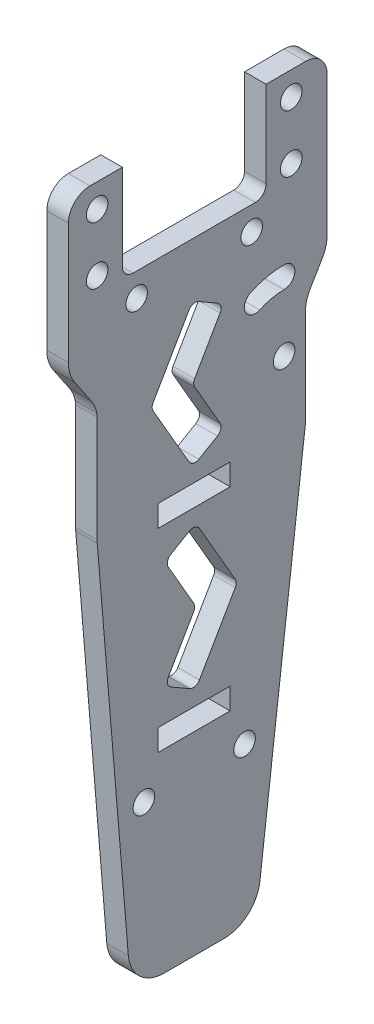
SolidWorks part; units mm, degrees
ref_plane "Płaszczyzna przednia" through (0, 0, 0) normal (0, 0, 1) x (1, 0, 0)
ref_plane "Płaszczyzna górna" through (0, 0, 0) normal (0, 1, 0) x (1, 0, 0)
ref_plane "Płaszczyzna prawa" through (0, 0, 0) normal (1, 0, 0) x (0, 0, -1)
ref_plane "Płaszczyzna1" through (-2, 0, 0) normal (-1, 0, 0) x (0, -1, 0)
sketch "Szkic1" plane through (-2, 0, 0) normal (-1, 0, 0) x (0, -1, 0)
  line L2 (-20.2446, -15.5) -> (-6.8721, -15.5)
  line L3 (-6.2672, -15.4633) -> (45.605, -9.1406)
  line L4 (50, -4.1773) -> (50, 4.1773)
  line L5 (45.4155, 9.16) -> (-6.4254, 13.4827)
  line L6 (-6.8408, 13.5) -> (-21.6327, 13.5)
  line L7 (-24.0036, 14.3214) -> (-27.4134, 16.6366)
  line L8 (-30.2221, 17.5) -> (-47, 17.5)
  line L9 (-50, 14.5) -> (-50, 10)
  line L10 (-50, 10) -> (-38, 10)
  line L11 (-36.5, 8.5) -> (-36.5, -8.5)
  line L12 (-38, -10) -> (-50, -10)
  line L13 (-50, -10) -> (-50, -15.5)
  line L14 (-47, -18.5) -> (-27.6426, -18.5)
  line L15 (-25.1042, -17.8077) -> (-22.283, -16.1452)
  line L16 (-46.7, 13.5) -> (-46.7, -13.5) construction
  line L17 (-33.2, 8) -> (-33.2, -8) construction
  line L18 (-38.7, 13.5) -> (-38.7, -13.5) construction
  line L19 (0, 0) -> (50, 0) construction
  line L20 (0, 0) -> (-45, 0) construction
  circle A0 centre (-46.7, -13.5) radius 1.5
  circle A1 centre (-38.7, -13.5) radius 1.5
  circle A2 centre (-33.2, -8) radius 1.5
  circle A3 centre (-33.2, 8) radius 1.5
  circle A4 centre (-38.7, 13.5) radius 1.5
  circle A5 centre (-46.7, 13.5) radius 1.5
  arc A6 (-6.4254, 13.4827) -> (-6.8408, 13.5) centre (-6.8408, 8.5) ccw
  arc A7 (-6.8721, -15.5) -> (-6.2672, -15.4633) centre (-6.8721, -10.5) ccw
  arc A12 (-22.283, -16.1452) -> (-20.6825, -15.5417) centre (-19.7445, -20.4529) cw
  arc A13 (45.605, -9.1406) -> (50, -4.1773) centre (45, -4.1773) ccw
  arc A14 (50, 4.1773) -> (45.4155, 9.16) centre (45, 4.1773) ccw
  arc A15 (-22.1331, 13.5467) -> (-24.0036, 14.3214) centre (-21.1949, 18.4579) cw
  arc A16 (-27.4134, 16.6366) -> (-30.2221, 17.5) centre (-30.2221, 12.5) ccw
  arc A17 (-47, 17.5) -> (-50, 14.5) centre (-47, 14.5) ccw
  arc A18 (-38, 10) -> (-36.5, 8.5) centre (-38, 8.5) cw
  arc A19 (-36.5, -8.5) -> (-38, -10) centre (-38, -8.5) cw
  arc A20 (-50, -15.5) -> (-47, -18.5) centre (-47, -15.5) ccw
  arc A21 (-27.6426, -18.5) -> (-25.1042, -17.8077) centre (-27.6426, -13.5) ccw
  spline S0 degree 3 poles (-20.2446, -15.5) (-20.3911, -15.5) (-20.5371, -15.5139) (-20.6825, -15.5417) knots 0 0 0 0 1 1 1 1
  spline S1 degree 3 poles (-22.1331, 13.5467) (-21.97, 13.5156) (-21.8032, 13.5) (-21.6327, 13.5) knots 0 0 0 0 1 1 1 1
  point P17 (-6.6327, 13.5)
  dimension "D8" = 5
  dimension "D9" = 5
  dimension "D11" = 5
  dimension "D15" = 3.3
  dimension "D1" = 13.5
  dimension "D2" = 8
  dimension "D3" = 16
  dimension "D4" = 100
  dimension "D5" = 50
  dimension "D6" = 20
  dimension "D7" = 15
  dimension "D10" = 29
  dimension "D16" = 16.8
  dimension "D17" = 13.5
  dimension "D18" = 36
  dimension "D19" = 17.5
extrude "Dodanie-wyciągnięcie1" add sketch "Szkic1" against normal blind 3
sketch "Szkic6" plane through (1, 0, 0) normal (1, 0, 0) x (0, 0, -1)
  line L0 (-5, 4) -> (-5, -20) construction
  line L1 (-5, 7) -> (5, 7)
  line L2 (-5, 7) -> (-5, 4)
  line L3 (-5, 4) -> (5, 4)
  line L4 (5, 7) -> (5, 4)
  line L5 (-5, -20) -> (5, -20)
  line L6 (-5, -20) -> (-5, -23)
  line L7 (-5, -23) -> (5, -23)
  line L8 (5, -20) -> (5, -23)
  dimension "D1" = 3
  dimension "D2" = 3
  dimension "D3" = 10
  dimension "D4" = 10
  dimension "D5" = 5
  dimension "D6" = 4
  dimension "D7" = 24
sketch "Szkic9" plane through (1, 0, 0) normal (1, 0, 0) x (0, 0, -1)
  line L2 (12.5, 16) -> (12.5, 25.5) construction
  line L3 (12.5, 16) -> (8.4851, 24.6099) construction
  circle A0 centre (12.5, 16) radius 1.5
  arc A1 (12.5, 25.5) -> (8.4851, 24.6099) centre (12.5, 16) ccw construction
  arc A2 (12.5, 27) -> (7.8512, 25.9694) centre (12.5, 16) ccw
  arc A3 (12.5, 24) -> (9.1191, 23.2505) centre (12.5, 16) ccw
  arc A4 (12.5, 24) -> (12.5, 27) centre (12.5, 25.5) ccw
  arc A5 (7.8512, 25.9694) -> (9.1191, 23.2505) centre (8.4851, 24.6099) ccw
  point P5 (10.4438, 25.2748)
  dimension "D3" = 25
  dimension "D4" = 9.5
  dimension "D1" = 3
  dimension "D5" = 1.5
  dimension "D2" = 9.5
extrude "Wytnij-wyciągnięcie4" cut sketch "Szkic9" against normal through all
extrude "Wytnij-wyciągnięcie1" cut sketch "Szkic6" against normal blind 10
sketch "Szkic7" plane through (1, 0, 0) normal (1, 0, 0) x (0, 0, -1)
  line L0 (6, -8) -> (0.2265, 2)
  line L1 (6, -8) -> (0.2265, -18)
  line L2 (0.2265, -18) -> (-4.1036, -15.5)
  line L3 (-4.1036, -15.5) -> (0.2265, -8)
  line L4 (0.2265, -8) -> (-4.1036, -0.5)
  line L5 (-4.1036, -0.5) -> (0.2265, 2)
  line L6 (-5, 4) -> (5, 4) construction
  line L7 (0, 0) -> (0, -30.3763) construction
  line L8 (5, 5.5) -> (-5, 5.5) construction
  line L9 (5, 4) -> (5, 7) construction
  line L10 (-5, 7) -> (-5, 4) construction
  line L11 (0, 7) -> (0, 4) construction
  line L12 (5, 7) -> (-5, 7) construction
  line L13 (-6, 19) -> (-0.2265, 9)
  line L14 (-6, 19) -> (-0.2265, 29)
  line L15 (4.1036, 26.5) -> (-0.2265, 19)
  line L16 (-0.2265, 19) -> (4.1036, 11.5)
  line L17 (4.1036, 11.5) -> (-0.2265, 9)
  line L18 (-0.2265, 29) -> (4.1036, 26.5)
  point P21 (0, 5.5)
  point P31 (0, 5.5)
  dimension "D1" = 30
  dimension "D2" = 30
  dimension "D3" = 10
  dimension "D4" = 10
  dimension "D5" = 12
  dimension "D6" = 6
  dimension "D7" = 5
  dimension "D8" = 5
  dimension "D9" = 2
extrude "Wytnij-wyciągnięcie2" cut sketch "Szkic7" against normal blind 10
fillet "Zaokrąglenie1" radius 1 12 edges at (-0.5, -8, -6) (-0.5, -18, -0.2265) (-0.5, -15.5, 4.1036) (-0.5, -8, -0.2265) (-0.5, -0.5, 4.1036) (-0.5, 2, -0.2265) (-0.5, 29, 0.2265) (-0.5, 26.5, -4.1036) (-0.5, 19, 0.2265) (-0.5, 11.5, -4.1036) (-0.5, 9, 0.2265) (-0.5, 19, 6)
sketch "Szkic8" plane through (-2, 0, 0) normal (-1, 0, 0) x (0, 0, 1)
  line L0 (0, -50) -> (0, -24.5205) construction
  line L1 (-4.1773, -50) -> (4.1773, -50) construction
  line L2 (-5, -23) -> (5, -23) construction
  circle A0 centre (7, -28) radius 1.5
  circle A1 centre (-7, -28) radius 1.5
  dimension "D1" = 3
  dimension "D2" = 14
  dimension "D3" = 5
extrude "Wytnij-wyciągnięcie3" cut sketch "Szkic8" against normal blind 10
